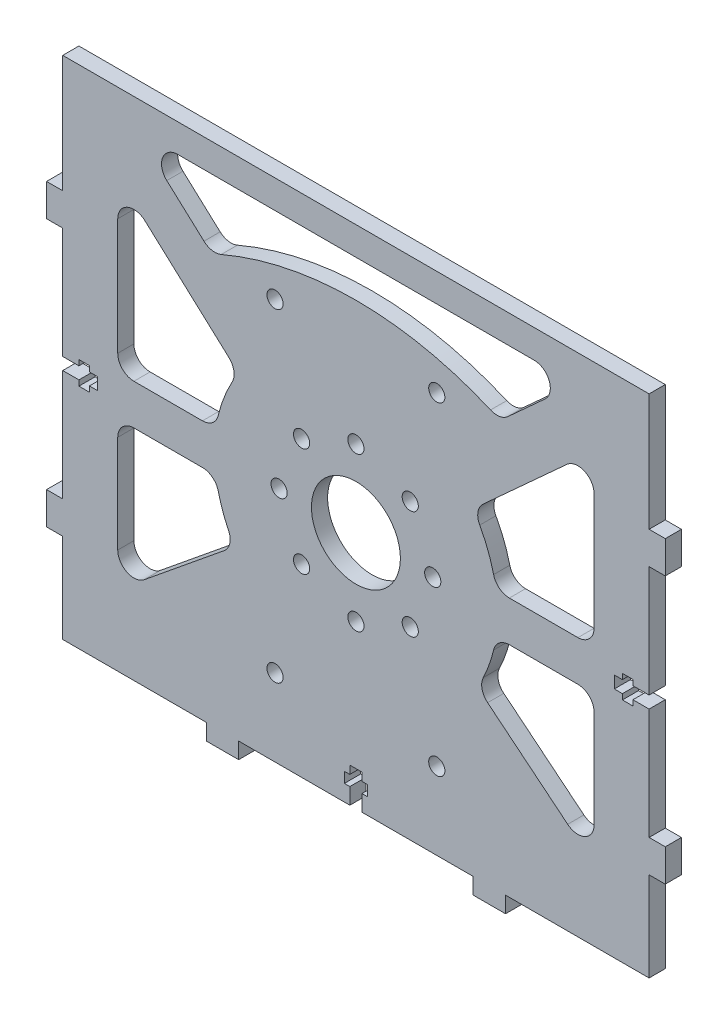
SolidWorks part; units mm, degrees
ref_plane "前视基准面" through (0, 0, 0) normal (0, 0, 1) x (1, 0, 0)
ref_plane "上视基准面" through (0, 0, 0) normal (0, 1, 0) x (1, 0, 0)
ref_plane "右视基准面" through (0, 0, 0) normal (1, 0, 0) x (0, 0, -1)
sketch "草图1" plane through (0, 0, 0) normal (0, 0, 1) x (1, 0, 0)
  line L9 (145, 64.5) -> (149, 64.5)
  line L10 (149, 64.5) -> (149, 63.15)
  line L11 (149, 63.15) -> (151.6, 63.15)
  line L12 (151.6, 63.15) -> (151.6, 64.5)
  line L13 (151.6, 64.5) -> (153.6, 64.5)
  line L14 (153.6, 64.5) -> (153.6, 67.5)
  line L23 (145, 66) -> (143.6922, 66) construction
  line L24 (145, 64.5) -> (145, 66) construction
  line L25 (151.6, 68.85) -> (151.6, 67.5)
  line L26 (149, 67.5) -> (149, 68.85)
  line L27 (151.6, 67.5) -> (153.6, 67.5)
  line L28 (149, 68.85) -> (151.6, 68.85)
  line L29 (145, 67.5) -> (149, 67.5)
  line L31 (145, 29) -> (141, 29)
  line L32 (141, 29) -> (141, 37)
  line L33 (141, 37) -> (145, 37)
  line L34 (145, 37) -> (145, 64.5)
  line L35 (141, 33) -> (142.703, 33) construction
  line L36 (145, 103) -> (141, 103)
  line L37 (145, 132) -> (145, 103)
  line L38 (141, 103) -> (141, 95)
  line L39 (141, 95) -> (145, 95)
  line L40 (145, 95) -> (145, 67.5)
  line L42 (145, 6.9) -> (145, 29)
  line L43 (294, 33) -> (292.297, 33) construction
  line L44 (290, 64.5) -> (290, 66) construction
  line L45 (290, 66) -> (291.3078, 66) construction
  line L47 (290, 95) -> (290, 67.5)
  line L48 (294, 95) -> (290, 95)
  line L49 (294, 103) -> (294, 95)
  line L50 (290, 132) -> (290, 103)
  line L51 (290, 103) -> (294, 103)
  line L52 (290, 37) -> (290, 64.5)
  line L53 (294, 37) -> (290, 37)
  line L54 (294, 29) -> (294, 37)
  line L55 (290, 29) -> (294, 29)
  line L57 (290, 67.5) -> (286, 67.5)
  line L58 (286, 68.85) -> (283.4, 68.85)
  line L59 (283.4, 67.5) -> (281.4, 67.5)
  line L60 (286, 67.5) -> (286, 68.85)
  line L61 (283.4, 68.85) -> (283.4, 67.5)
  line L62 (281.4, 64.5) -> (281.4, 67.5)
  line L63 (283.4, 64.5) -> (281.4, 64.5)
  line L64 (283.4, 63.15) -> (283.4, 64.5)
  line L65 (286, 63.15) -> (283.4, 63.15)
  line L66 (286, 64.5) -> (286, 63.15)
  line L67 (290, 64.5) -> (286, 64.5)
  line L68 (145, 132) -> (290, 132)
  line L69 (281.4, 66) -> (153.6, 66) construction
  line L70 (217.5, 6.9) -> (217.5, 25.4388) construction
  line L73 (217.5, 6.9) -> (217.5, 5.5922) construction
  line L99 (246.5, 6.9) -> (219, 6.9)
  line L100 (246.5, 2.9) -> (246.5, 6.9)
  line L101 (254.5, 2.9) -> (246.5, 2.9)
  line L102 (283.5, 6.9) -> (254.5, 6.9)
  line L103 (254.5, 6.9) -> (254.5, 2.9)
  line L104 (188.5, 6.9) -> (216, 6.9)
  line L105 (188.5, 2.9) -> (188.5, 6.9)
  line L106 (180.5, 2.9) -> (188.5, 2.9)
  line L107 (180.5, 6.9) -> (180.5, 2.9)
  line L108 (151.5, 6.9) -> (180.5, 6.9)
  line L109 (219, 6.9) -> (219, 10.9)
  line L110 (220.35, 10.9) -> (220.35, 13.5)
  line L111 (219, 13.5) -> (219, 15.5)
  line L112 (219, 10.9) -> (220.35, 10.9)
  line L113 (220.35, 13.5) -> (219, 13.5)
  line L114 (216, 15.5) -> (219, 15.5)
  line L115 (216, 13.5) -> (216, 15.5)
  line L116 (214.65, 13.5) -> (216, 13.5)
  line L117 (214.65, 10.9) -> (214.65, 13.5)
  line L118 (216, 10.9) -> (214.65, 10.9)
  line L119 (216, 6.9) -> (216, 10.9)
  line L120 (283.5, 6.9) -> (290, 6.9)
  line L121 (151.5, 6.9) -> (145, 6.9)
  line L122 (290, 29) -> (290, 6.9)
  circle A6 centre (217.5, 66) radius 19 construction
  circle A7 centre (217.5, 47) radius 2
  circle A8 centre (204.065, 52.565) radius 2
  circle A9 centre (198.5, 66) radius 2
  circle A10 centre (204.065, 79.435) radius 2
  circle A11 centre (217.5, 85) radius 2
  circle A12 centre (230.935, 79.435) radius 2
  circle A13 centre (236.5, 66) radius 2
  circle A14 centre (230.935, 52.565) radius 2
  circle A15 centre (217.5, 66) radius 11
  circle A19 centre (197.5, 106) radius 2
  circle A20 centre (237.5, 106) radius 2
  circle A22 centre (237.5, 26) radius 2
  circle A23 centre (197.5, 26) radius 2
  point P15 (144.3461, 66)
  dimension "D2" = 8
  dimension "D3" = 4
  dimension "D4" = 2
  dimension "D5" = 2.6
  dimension "D6" = 1.35
  dimension "D8" = 1.5
extrude "凸台-拉伸1" add sketch "草图1" along normal blind 4
sketch "草图2" plane through (290, 0, 0) normal (1, 0, 0) x (0, 0, -1)
  line L0 (-2, 67.5) -> (-2, 64.5)
  line L1 (-4, 67.5) -> (0, 67.5) construction
  line L2 (-4, 64.5) -> (0, 64.5) construction
  circle A0 centre (-2, 66) radius 1.5
sketch "草图3" plane through (0, 0, 0) normal (0, 0, -1) x (-1, 0, 0)
  line L19 (-255.4473, 61) -> (-272.4, 61)
  line L22 (-269.7073, 106.7651) -> (-248.9271, 87.848)
  line L25 (-255.4473, 71) -> (-272.4, 71)
  line L26 (-276.4, 75) -> (-276.4, 103.8072)
  line L29 (-276.4, 57) -> (-276.4, 32.8585)
  line L30 (-158.6, 57) -> (-158.6, 32.8585)
  line L31 (-165.1274, 29.7581) -> (-184.9279, 45.8989)
  line L32 (-269.8726, 29.7581) -> (-250.0721, 45.8989)
  line L33 (-217.5, 66) -> (-217.5, 58.7222) construction
  line L34 (-179.5527, 61) -> (-162.6, 61)
  line L35 (-179.5527, 71) -> (-162.6, 71)
  line L36 (-158.6, 75) -> (-158.6, 103.8072)
  line L37 (-165.2927, 106.7651) -> (-186.0729, 87.848)
  line L38 (-241.9948, 97.7648) -> (-264.269, 118.0421) construction
  line L39 (-261.5763, 125) -> (-173.4237, 125)
  line L40 (-193.0052, 97.7648) -> (-170.731, 118.0421) construction
  line L41 (-179.9299, 109.6679) -> (-170.731, 118.0421)
  line L42 (-255.0701, 109.6679) -> (-264.269, 118.0421)
  line L52 (-191.3089, 35.6186) -> (-183.9261, 29.6004) construction
  line L54 (-248.5465, 22.5) -> (-186.4535, 22.5) construction
  line L55 (-243.6911, 35.6186) -> (-251.0739, 29.6004) construction
  circle A10 centre (-217.5, 66) radius 30 construction
  arc A11 (-251.5553, 74.0769) -> (-248.1204, 82.9526) centre (-217.5, 66) cw
  arc A13 (-269.8726, 29.7581) -> (-276.4, 32.8585) centre (-272.4, 32.8585) cw
  arc A14 (-251.5553, 57.9231) -> (-248.9996, 50.7429) centre (-217.5, 66) ccw
  arc A15 (-276.4, 57) -> (-272.4, 61) centre (-272.4, 57) cw
  arc A16 (-250.0721, 45.8989) -> (-248.9996, 50.7429) centre (-252.5995, 48.9993) ccw
  arc A17 (-251.5553, 57.9231) -> (-255.4473, 61) centre (-255.4473, 57) ccw
  arc A18 (-251.5553, 74.0769) -> (-255.4473, 71) centre (-255.4473, 75) cw
  arc A19 (-272.4, 71) -> (-276.4, 75) centre (-272.4, 75) cw
  arc A20 (-276.4, 103.8072) -> (-269.7073, 106.7651) centre (-272.4, 103.8072) cw
  arc A21 (-248.1204, 82.9526) -> (-248.9271, 87.848) centre (-251.6199, 84.8901) ccw
  arc A22 (-183.4447, 57.9231) -> (-186.0004, 50.7429) centre (-217.5, 66) cw
  arc A23 (-184.9279, 45.8989) -> (-186.0004, 50.7429) centre (-182.4005, 48.9993) cw
  arc A24 (-183.4447, 57.9231) -> (-179.5527, 61) centre (-179.5527, 57) cw
  arc A25 (-165.1274, 29.7581) -> (-158.6, 32.8585) centre (-162.6, 32.8585) ccw
  arc A26 (-158.6, 57) -> (-162.6, 61) centre (-162.6, 57) ccw
  arc A27 (-183.4447, 74.0769) -> (-179.5527, 71) centre (-179.5527, 75) ccw
  arc A28 (-186.8796, 82.9526) -> (-186.0729, 87.848) centre (-183.3801, 84.8901) cw
  arc A29 (-158.6, 103.8072) -> (-165.2927, 106.7651) centre (-162.6, 103.8072) ccw
  arc A30 (-162.6, 71) -> (-158.6, 75) centre (-162.6, 75) ccw
  arc A31 (-183.4447, 74.0769) -> (-186.8796, 82.9526) centre (-217.5, 66) ccw
  arc A33 (-237.175, 97.3352) -> (-197.825, 97.3352) centre (-217.5, 66) cw construction
  arc A34 (-186.4535, 22.5) -> (-183.9261, 29.6004) centre (-186.4535, 26.5) ccw construction
  arc A35 (-197.825, 97.3352) -> (-193.0052, 97.7648) centre (-195.6979, 100.7228) ccw construction
  arc A36 (-237.175, 97.3352) -> (-241.9948, 97.7648) centre (-239.3021, 100.7228) cw construction
  arc A37 (-264.269, 118.0421) -> (-261.5763, 125) centre (-261.5763, 121) cw
  arc A38 (-170.731, 118.0421) -> (-173.4237, 125) centre (-173.4237, 121) ccw
  arc A40 (-238.8551, 35.7848) -> (-196.1449, 35.7848) centre (-217.5, 66) ccw construction
  arc A41 (-191.3089, 35.6186) -> (-196.1449, 35.7848) centre (-193.8363, 32.5182) ccw construction
  arc A42 (-248.5465, 22.5) -> (-251.0739, 29.6004) centre (-248.5465, 26.5) cw construction
  arc A43 (-243.6911, 35.6186) -> (-238.8551, 35.7848) centre (-241.1637, 32.5182) cw construction
  arc A44 (-184.2046, 108.952) -> (-250.7954, 108.952) centre (-217.5, 31.629) ccw
  arc A45 (-184.2046, 108.952) -> (-179.9299, 109.6679) centre (-182.6226, 112.6258) ccw
  arc A46 (-255.0701, 109.6679) -> (-250.7954, 108.952) centre (-252.3774, 112.6258) ccw
  point P83 (-181.8681, 107.9035)
  point P87 (-253.1319, 107.9035)
  dimension "D4" = 4
  dimension "D1" = 4
  dimension "D3" = 4
  dimension "D2" = 4
extrude "切除-拉伸2" cut sketch "草图3" against normal blind 4
sketch "草图4" plane through (145, 0, 0) normal (-1, 0, 0) x (0, 0, 1)
  line L0 (2, 67.5) -> (2, 64.5)
  line L1 (4, 67.5) -> (0, 67.5) construction
  line L2 (4, 64.5) -> (0, 64.5) construction
  circle A0 centre (2, 66) radius 1.5
